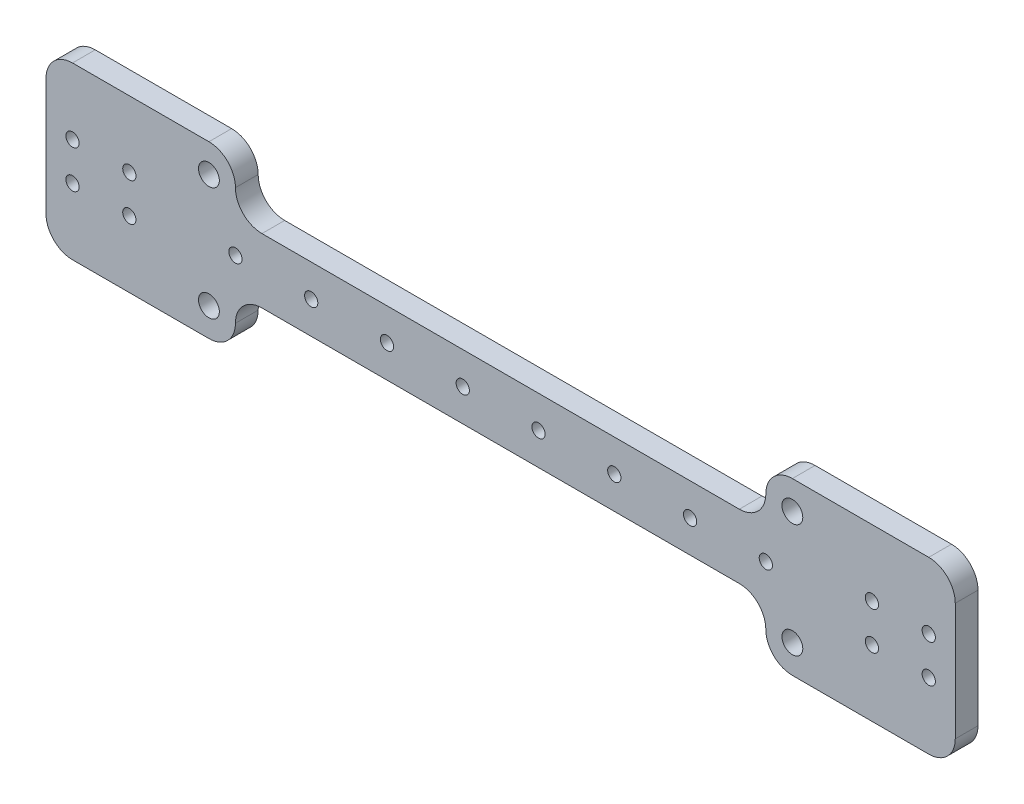
SolidWorks part; units mm, degrees
ref_plane "Front Plane" through (0, 0, 0) normal (0, 0, 1) x (1, 0, 0)
ref_plane "Top Plane" through (0, 0, 0) normal (0, 1, 0) x (1, 0, 0)
ref_plane "Right Plane" through (0, 0, 0) normal (1, 0, 0) x (0, 0, -1)
sketch "Sketch1" plane through (0, 0, 0) normal (0, 0, 1) x (1, 0, 0)
  line L0 (0, 0) -> (226, 0)
  line L1 (0, -5) -> (20.3842, -5) construction
  line L2 (0, 0) -> (15, 0)
  line L3 (0, 0) -> (0, -10)
  line L4 (0, -10) -> (15, -10)
  line L5 (15, 0) -> (15, -10)
  line L6 (113, 0) -> (113, -60.9207) construction
  line L8 (-7, -17.5) -> (233, -17.5)
  line L9 (-7, -17.5) -> (-7, 7.5)
  line L10 (-7, 7.5) -> (233, 7.5)
  line L11 (233, -17.5) -> (233, 7.5)
  line L12 (-7, -17.5) -> (233, 7.5) construction
  line L13 (-7, 7.5) -> (233, -17.5) construction
  line L14 (35.5, -0.5) -> (190.5, -0.5)
  line L15 (35.5, -0.5) -> (35.5, -9.5)
  line L16 (35.5, -9.5) -> (190.5, -9.5)
  line L17 (190.5, -0.5) -> (190.5, -9.5)
  line L18 (35.5, -0.5) -> (190.5, -9.5) construction
  line L19 (35.5, -9.5) -> (190.5, -0.5) construction
  circle A0 centre (0, 0) radius 1.75
  circle A1 centre (226, 0) radius 1.75
  circle A2 centre (15, 0) radius 1.75
  circle A3 centre (0, -10) radius 1.75
  circle A4 centre (15, -10) radius 1.75
  circle A5 centre (211, 0) radius 1.75
  circle A6 centre (211, -10) radius 1.75
  circle A7 centre (226, -10) radius 1.75
  circle A8 centre (183, -5) radius 1.75
  circle A9 centre (163, -5) radius 1.75
  circle A10 centre (143, -5) radius 1.75
  circle A11 centre (123, -5) radius 1.75
  circle A12 centre (103, -5) radius 1.75
  circle A13 centre (83, -5) radius 1.75
  circle A14 centre (63, -5) radius 1.75
  circle A15 centre (43, -5) radius 1.75
  point P21 (113, -5)
  point P27 (113, -5)
  dimension "D1" = 3.5
  dimension "D3" = 3.5
  dimension "D6" = 3.5
  dimension "D12" = 3.5
  dimension "D2" = 226
  dimension "D4" = 15
  dimension "D5" = 10
  dimension "D7" = 240
  dimension "D8" = 25
  dimension "D9" = 5
  dimension "D10" = 155
  dimension "D11" = 9
  dimension "D13" = 7.5
  dimension "D14" = 4.5
  dimension "D15" = 8
extrude "Boss-Extrude1" add sketch "Sketch1" along normal blind 6 contours L8 L11 L10 L9 A7 A6 L14 L17 L16 L15 A5 A2 L5 A4 L4 A3 L3 A0 L2 A1 | L4 A4 L5 A2 L2 A0 L3 A3 | L17 L14 L15 L16 A15 A14 A13 A12 A11 A10 A9 A8 region at (7.5, -5, 0) region at (-4.587, -5, 0) region at (113, -5, 0)
sketch "Sketch2" plane through (0, 0, 6) normal (0, 0, 1) x (1, 0, 0)
  line L0 (113, 7.5) -> (113, 59.5119)
  line L1 (-7, -17.5) -> (43, -17.5)
  line L2 (-7, -17.5) -> (-7, -27.5)
  line L3 (-7, -27.5) -> (43, -27.5)
  line L4 (43, -17.5) -> (43, -27.5)
  line L5 (-7, 7.5) -> (43, 7.5)
  line L6 (-7, 7.5) -> (-7, 17.5)
  line L7 (-7, 17.5) -> (43, 17.5)
  line L8 (43, 7.5) -> (43, 17.5)
  line L9 (-7, 7.5) -> (233, 7.5) construction
  line L10 (183, 7.5) -> (183, 17.5)
  line L11 (233, 17.5) -> (183, 17.5)
  line L12 (233, 7.5) -> (233, 17.5)
  line L13 (233, 7.5) -> (183, 7.5)
  line L14 (183, -17.5) -> (183, -27.5)
  line L15 (233, -27.5) -> (183, -27.5)
  line L16 (233, -17.5) -> (233, -27.5)
  line L17 (233, -17.5) -> (183, -17.5)
  line M17 (-7, -17.5) -> (233, -17.5)
  line M19 (233, 7.5) -> (-7, 7.5)
  dimension "D1" = 10
  dimension "D2" = 50
  dimension "D3" = 10
  dimension "D4" = 50
extrude "Boss-Extrude2" add sketch "Sketch2" against normal blind 6 contours L4 L2 L3 M17 | L8 L7 L6 M19 | L12 L11 L10 M19 | L16 L14 L15 M17 region at (208, -22.5, 6) region at (18, -22.5, 6) region at (18, 12.5, 6) region at (208, 12.5, 6)
sketch "Sketch3" plane through (0, 0, 0) normal (0, 0, -1) x (-1, 0, 0)
  line L1 (-183, 7.5) -> (-43, 7.5)
  line L2 (-183, 7.5) -> (-183, 3.5)
  line L3 (-183, 3.5) -> (-43, 3.5)
  line L4 (-43, 7.5) -> (-43, 3.5)
  line L5 (-183, -17.5) -> (-43, -17.5)
  line L6 (-183, -17.5) -> (-183, -13.5)
  line L7 (-183, -13.5) -> (-43, -13.5)
  line L8 (-43, -17.5) -> (-43, -13.5)
  dimension "D1" = 4
  dimension "D2" = 4
extrude "Cut-Extrude1" cut sketch "Sketch3" against normal through all
sketch "Sketch4" plane through (0, 0, 6) normal (0, 0, 1) x (1, 0, 0)
  line L0 (15, 0) -> (36, 0) construction
  line L1 (36, 0) -> (36, -20)
  line L2 (-7, -5) -> (39.1948, -5)
  line L3 (-7, -27.5) -> (-7, 17.5) construction
  line L4 (113, 3.5) -> (113, -45.3452) construction
  line L5 (183, 3.5) -> (43, 3.5) construction
  circle A0 centre (36, -20) radius 2.75
  circle A1 centre (36, 10) radius 2.75
  circle A2 centre (190, 10) radius 2.75
  circle A3 centre (190, -20) radius 2.75
  dimension "D2" = 5.5
  dimension "D1" = 21
  dimension "D3" = 20
extrude "Cut-Extrude2" cut sketch "Sketch4" against normal through all contours A0 | A1 | A3 | A2
fillet "Fillet1" radius 7 12 edges at (183, 3.5, 3) (183, 17.5, 3) (233, 17.5, 3) (233, -27.5, 3) (183, -13.5, 3) (183, -27.5, 3) (43, -13.5, 3) (43, 3.5, 3) (43, 17.5, 3) (-7, 17.5, 3) (43, -27.5, 3) (-7, -27.5, 3)
